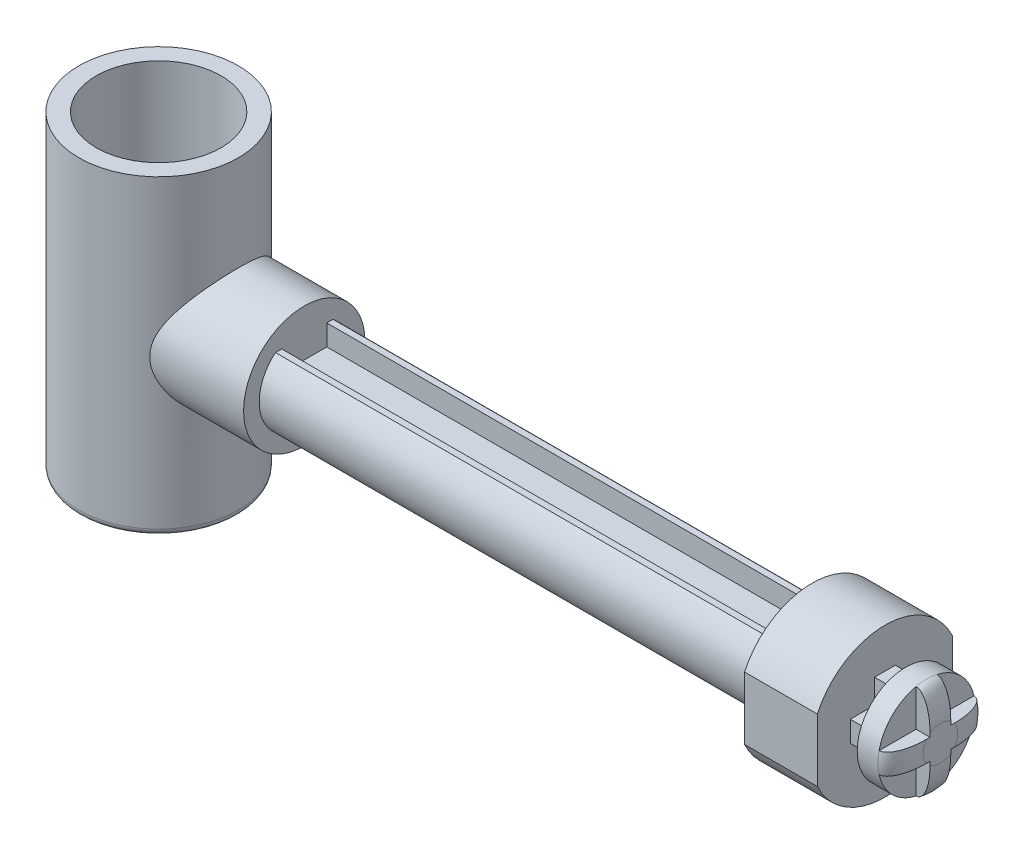
SolidWorks part; units mm, degrees
ref_plane "Front Plane" through (0, 0, 0) normal (0, 0, 1) x (1, 0, 0)
ref_plane "Top Plane" through (0, 0, 0) normal (0, 1, 0) x (1, 0, 0)
ref_plane "Right Plane" through (0, 0, 0) normal (1, 0, 0) x (0, 0, -1)
sketch "Sketch1" plane through (0, 0, 0) normal (1, 0, 0) x (0, 0, -1)
  circle A0 centre (0, 0) radius 4.3
  dimension "D1" = 8.6
extrude "Boss-Extrude1" add sketch "Sketch1" along normal blind 4.2
sketch "Sketch3" plane through (4.2, 0, 0) normal (1, 0, 0) x (0, 0, -1)
  line L1 (2, -0.6) -> (-2, -0.6)
  line L2 (2, -0.6) -> (2, 0.6)
  line L3 (2, 0.6) -> (-2, 0.6)
  line L4 (-2, -0.6) -> (-2, 0.6)
  line L5 (2, -0.6) -> (-2, 0.6) construction
  line L6 (2, 0.6) -> (-2, -0.6) construction
  line L7 (-0.6, -2) -> (0.6, -2)
  line L8 (-0.6, -2) -> (-0.6, 2)
  line L9 (-0.6, 2) -> (0.6, 2)
  line L10 (0.6, -2) -> (0.6, 2)
  line L11 (-0.6, -2) -> (0.6, 2) construction
  line L12 (-0.6, 2) -> (0.6, -2) construction
  point P0 (0, 0)
  point P6 (0, 0)
  dimension "D1" = 1.2
  dimension "D2" = 4
extrude "Boss-Extrude2" add sketch "Sketch3" along normal blind 1.2 contours L3 L4 L1 L2 | L10 L9 L8 L7
sketch "Sketch4" plane through (5.4, 0, 0) normal (1, 0, 0) x (0, 0, -1)
  circle A0 centre (0, 0) radius 2.8
  dimension "D1" = 5.6
extrude "Boss-Extrude3" add sketch "Sketch4" along normal blind 1.2
sketch "Sketch5" plane through (6.6, 0, 0) normal (1, 0, 0) x (0, 0, -1)
  line L1 (2.8, -0.6) -> (-2.8, -0.6)
  line L2 (2.8, -0.6) -> (2.8, 0.6)
  line L3 (2.8, 0.6) -> (-2.8, 0.6)
  line L4 (-2.8, -0.6) -> (-2.8, 0.6)
  line L5 (2.8, -0.6) -> (-2.8, 0.6) construction
  line L6 (2.8, 0.6) -> (-2.8, -0.6) construction
  line L7 (0.6, -2.8) -> (-0.6, -2.8)
  line L8 (0.6, -2.8) -> (0.6, 2.8)
  line L9 (0.6, 2.8) -> (-0.6, 2.8)
  line L10 (-0.6, -2.8) -> (-0.6, 2.8)
  line L11 (0.6, -2.8) -> (-0.6, 2.8) construction
  line L12 (0.6, 2.8) -> (-0.6, -2.8) construction
  circle A0 centre (0, 0) radius 2.8 construction
  point P0 (0, 0)
  point P8 (0, 0)
  circle M9 centre (0, 0) radius 2.8
  dimension "D1" = 1.2
extrude "Boss-Extrude4" add sketch "Sketch5" along normal blind 0.8 contours L1 L10 L3 M9 | L10 L3 L8 M9 | L10 L8 L1 M9 | L8 L1 L3 M9 | L10 L1 L8 L3 region at (6.6, 0, -1.6893) region at (6.6, -1.6893, 0) region at (6.6, 0, 0) region at (6.6, 0, 1.6893) region at (6.6, 1.6893, 0)
fillet "Fillet1" radius 0.8 4 edges at (7.4, 0, -2.8) (7.4, 2.8, 0) (7.4, 0, 2.8) (7.4, -2.8, 0) second distance 1.8 first distance on face at (7, 0, 0)
sketch "Sketch6" plane through (0, 0, 0) normal (-1, 0, 0) x (0, 0, 1)
  circle A0 centre (0, 0) radius 2.6
  dimension "D1" = 5.2
extrude "Boss-Extrude5" add sketch "Sketch6" along normal blind 29.3
sketch "Sketch7" plane through (-29.3, 0, 0) normal (-1, 0, 0) x (0, 0, 1)
  circle A0 centre (0, 0) radius 3.5
  dimension "D1" = 7
extrude "Boss-Extrude6" add sketch "Sketch7" along normal blind 5.4
sketch "Sketch8" plane through (0, 0, 0) normal (0, 1, 0) x (1, 0, 0)
  line L0 (-29.3, -3.5) -> (-29.3, 3.5) construction
  circle A0 centre (-37.7, 0) radius 4.6
  dimension "D1" = 9.2
  dimension "D2" = 8.4
extrude "Boss-Extrude7" add sketch "Sketch8" along normal mid plane 18
sketch "Sketch9" plane through (0, 9, 0) normal (0, 1, 0) x (1, 0, 0)
  line L0 (-37.7, 4.6) -> (-37.7, -49995.4) construction
  line L1 (-42.3, 0) -> (49957.7, 0) construction
  circle A2 centre (-37.7, 0) radius 3.6
  dimension "D1" = 7.2
extrude "Cut-Extrude1" cut sketch "Sketch9" against normal blind 16
ref_plane "Plane1" through (0, 2, 0) normal (0, 1, 0) x (1, 0, 0)
sketch "Sketch10" plane through (0, 2, 0) normal (0, 1, 0) x (1, 0, 0)
  line L0 (-29.3, -2.6) -> (-29.3, 2.6) construction
  line L1 (-29.3, 2) -> (0, 2)
  line L2 (-29.3, 2) -> (-29.3, -2)
  line L3 (-29.3, -2) -> (0, -2)
  line L4 (0, 2) -> (0, -2)
  line L5 (0, 4.3) -> (0, -4.3) construction
  line L6 (-37.7, 0) -> (49962.3, 0) construction
  dimension "D1" = 4
extrude "Cut-Extrude2" cut sketch "Sketch10" along normal blind 1.2
sketch "Sketch11" plane through (0, 2, 0) normal (0, 1, 0) x (1, 0, 0)
  line L0 (-37.7, 0) -> (49962.3, 0) construction
  line L1 (-29.3, -3.5) -> (-29.3, 3.5) construction
  line L2 (-29.3, 1.3) -> (0, 1.3)
  line L3 (-29.3, 1.3) -> (-29.3, -1.3)
  line L4 (-29.3, -1.3) -> (0, -1.3)
  line L5 (0, 1.3) -> (0, -1.3)
  line L6 (0, -1.6613) -> (0, 1.6613) construction
  dimension "D1" = 2.6
extrude "Cut-Extrude3" cut sketch "Sketch11" against normal blind 1.2
mirror "Mirror1" about plane through (0, 0, 0) normal (0, 1, 0) of "Cut-Extrude3", "Cut-Extrude2"
fillet "Fillet2" radius 0.4 1 edges at (-37.7, -9, 4.6)
sketch "Sketch12" plane through (4.2, 0, 0) normal (1, 0, 0) x (0, 0, -1)
  line L1 (3.9, -6) -> (-3.9, -6) construction
  line L2 (3.9, -6) -> (3.9, 6) construction
  line L3 (3.9, 6) -> (-3.9, 6) construction
  line L4 (-3.9, -6) -> (-3.9, 6) construction
  line L5 (3.9, -6) -> (-3.9, 6) construction
  line L6 (3.9, 6) -> (-3.9, -6) construction
  line L7 (-3.9, 6) -> (-4.9, 6)
  line L8 (-3.9, 6) -> (-3.9, -6)
  line L9 (-3.9, -6) -> (-4.9, -6)
  line L10 (-4.9, 6) -> (-4.9, -6)
  line L11 (3.9, 6) -> (4.9, 6)
  line L12 (3.9, 6) -> (3.9, -6)
  line L13 (3.9, -6) -> (4.9, -6)
  line L14 (4.9, 6) -> (4.9, -6)
  point P0 (0, 0)
  circle M25 centre (0, 0) radius 4.3
  dimension "D1" = 7.8
  dimension "D2" = 12
  dimension "D3" = 1
extrude "Cut-Extrude5" cut sketch "Sketch12" against normal up to surface (4.2 mm away) contours L8 M25 | L12 M25 region at (4.2, 0, 4.0607) region at (4.2, 0, -4.0607) up to face at (0, 0, 0)
